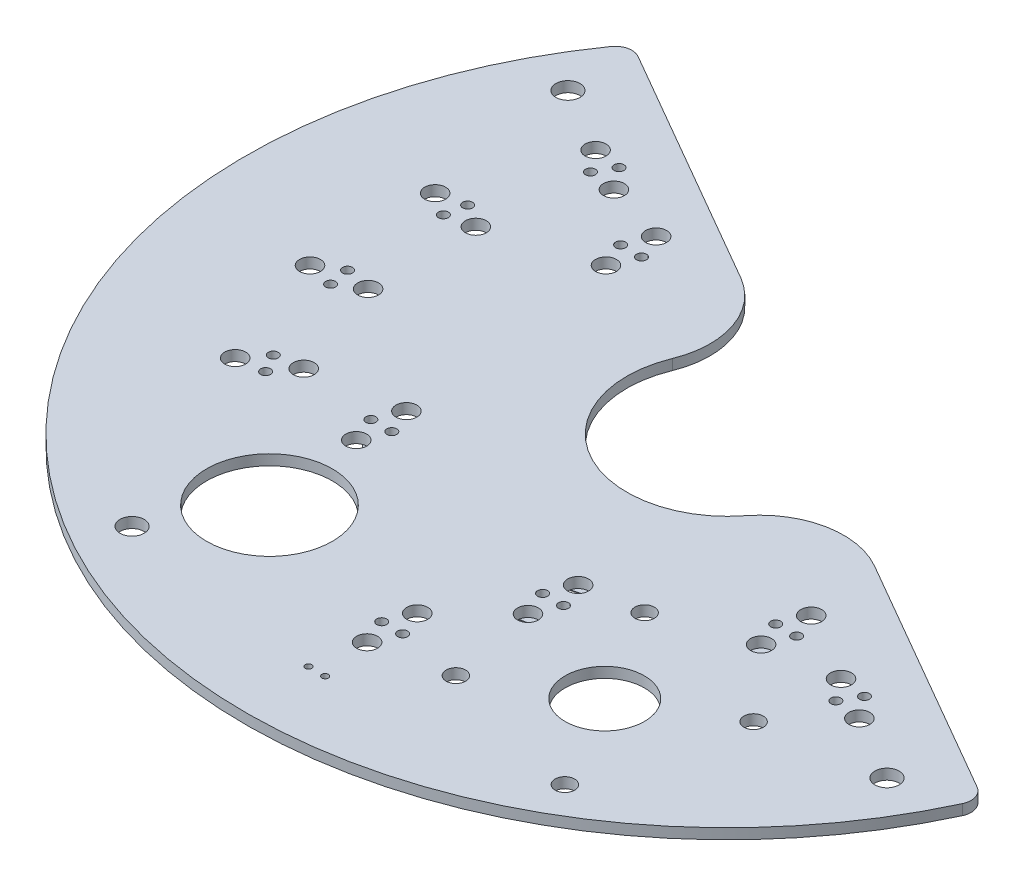
SolidWorks part; units mm, degrees
ref_plane "Front Plane" through (0, 0, 0) normal (0, 0, 1) x (1, 0, 0)
ref_plane "Top Plane" through (0, 0, 0) normal (0, 1, 0) x (1, 0, 0)
ref_plane "Right Plane" through (0, 0, 0) normal (1, 0, 0) x (0, 0, -1)
sketch "Sketch1" plane through (0, 0, 0) normal (0, 1, 0) x (1, 0, 0)
  line L0 (0, 50.8) -> (0, 59.6199) construction
  line L1 (0, 50.8) -> (11.3081, 50.8) construction
  line L2 (0, 0) -> (0, 47) construction
  line L3 (0, 0) -> (-46.286, 8.1615) construction
  line L4 (0, 0) -> (0, 47) construction
  line L5 (0, 0) -> (-46.286, -8.1615) construction
  line L6 (30.1421, -21.2511) -> (30.1421, -12.4312) construction
  line L7 (8.4732, -34.8981) -> (8.4732, -26.0782) construction
  line L8 (-27.3518, -25.0898) -> (-27.3518, -16.2699) construction
  line L9 (-31.3513, 16.7436) -> (-31.3513, 25.5635) construction
  circle A0 centre (0, 0) radius 50.8 construction
  circle A1 centre (0, 0) radius 15.24
  circle A2 centre (0, 0) radius 73.025
  circle A3 centre (0, 50.8) radius 6.3 construction
  circle A4 centre (25.4, 43.9941) radius 6.3 construction
  circle A5 centre (43.9941, 25.4) radius 6.3 construction
  circle A6 centre (50.8, 0) radius 6.3 construction
  circle A7 centre (43.9941, -25.4) radius 6.3 construction
  circle A8 centre (25.4, -43.9941) radius 6.3 construction
  circle A9 centre (0, -50.8) radius 6.3 construction
  circle A10 centre (-25.4, -43.9941) radius 6.3 construction
  circle A11 centre (-43.9941, -25.4) radius 6.3 construction
  circle A12 centre (-50.8, 0) radius 6.3 construction
  circle A13 centre (-43.9941, 25.4) radius 6.3 construction
  circle A14 centre (-25.4, 43.9941) radius 6.3 construction
  circle A15 centre (0, 50.8) radius 1.585 construction
  circle A16 centre (-1.585, 50.8) radius 0.75
  circle A17 centre (1.585, 50.8) radius 0.75
  circle A18 centre (0, 50.8) radius 3.8 construction
  circle A19 centre (0, 54.6) radius 1.585
  circle A20 centre (0, 47) radius 1.585
  circle A21 centre (47.285, 27.3) radius 1.585
  circle A22 centre (43.2016, 26.7727) radius 0.75
  circle A23 centre (44.7866, 24.0273) radius 0.75
  circle A24 centre (40.7032, 23.5) radius 1.585
  circle A25 centre (47.285, -27.3) radius 1.585
  circle A26 centre (44.7866, -24.0273) radius 0.75
  circle A27 centre (43.2016, -26.7727) radius 0.75
  circle A28 centre (40.7032, -23.5) radius 1.585
  circle A29 centre (0, -54.6) radius 1.585
  circle A30 centre (1.585, -50.8) radius 0.75
  circle A31 centre (-1.585, -50.8) radius 0.75
  circle A32 centre (0, -47) radius 1.585
  circle A33 centre (-47.285, -27.3) radius 1.585
  circle A34 centre (-43.2016, -26.7727) radius 0.75
  circle A35 centre (-44.7866, -24.0273) radius 0.75
  circle A36 centre (-40.7032, -23.5) radius 1.585
  circle A37 centre (-47.285, 27.3) radius 1.585
  circle A38 centre (-44.7866, 24.0273) radius 0.75
  circle A39 centre (-43.2016, 26.7727) radius 0.75
  circle A40 centre (-40.7032, 23.5) radius 1.585
  circle A41 centre (25.4, 43.9941) radius 20
  circle A42 centre (-25.4, -43.9941) radius 9.525
  circle A43 centre (25.4, -43.9941) radius 6
  circle A44 centre (-46.286, 8.1615) radius 1.585
  circle A45 centre (-50.3035, 7.2604) radius 0.75
  circle A46 centre (-49.753, 10.3822) radius 0.75
  circle A47 centre (-53.7705, 9.4812) radius 1.585
  circle A48 centre (-46.286, -8.1615) radius 1.585
  circle A49 centre (-49.753, -10.3822) radius 0.75
  circle A50 centre (-50.3035, -7.2604) radius 0.75
  circle A51 centre (-53.7705, -9.4812) radius 1.585
  circle A52 centre (30.1421, -21.2511) radius 6.3 construction
  circle A53 centre (30.1421, -21.2511) radius 1.585 construction
  circle A54 centre (28.5571, -21.2511) radius 0.75
  circle A55 centre (31.7271, -21.2511) radius 0.75
  circle A56 centre (30.1421, -21.2511) radius 3.8 construction
  circle A57 centre (30.1421, -17.4511) radius 1.585
  circle A58 centre (30.1421, -25.0511) radius 1.585
  circle A59 centre (8.4732, -34.8981) radius 6.3 construction
  circle A60 centre (8.4732, -34.8981) radius 1.585 construction
  circle A61 centre (6.8882, -34.8981) radius 0.75
  circle A62 centre (10.0582, -34.8981) radius 0.75
  circle A63 centre (8.4732, -34.8981) radius 3.8 construction
  circle A64 centre (8.4732, -31.0981) radius 1.585
  circle A65 centre (8.4732, -38.6981) radius 1.585
  circle A66 centre (-27.3518, -25.0898) radius 6.3 construction
  circle A67 centre (-27.3518, -25.0898) radius 1.585 construction
  circle A68 centre (-28.9368, -25.0898) radius 0.75
  circle A69 centre (-25.7668, -25.0898) radius 0.75
  circle A70 centre (-27.3518, -25.0898) radius 3.8 construction
  circle A71 centre (-27.3518, -21.2898) radius 1.585
  circle A72 centre (-27.3518, -28.8898) radius 1.585
  circle A73 centre (-31.3513, 16.7436) radius 6.3 construction
  circle A74 centre (-31.3513, 16.7436) radius 1.585 construction
  circle A75 centre (-32.9363, 16.7436) radius 0.75
  circle A76 centre (-29.7663, 16.7436) radius 0.75
  circle A77 centre (-31.3513, 16.7436) radius 3.8 construction
  circle A78 centre (-31.3513, 20.5436) radius 1.585
  circle A79 centre (-31.3513, 12.9436) radius 1.585
  point P50 (0, 0)
  point P84 (0, 0)
  dimension "D1" = 12
  dimension "D2" = 101.6
  dimension "D3" = 3.17
  dimension "D4" = 1.5
  dimension "D5" = 7.6
  dimension "D6" = 6
  dimension "D7" = 3.17
  dimension "D8" = 40
  dimension "D9" = 19.05
  dimension "D10" = 12
  dimension "D11" = 146.05
  dimension "D12" = 30.48
  dimension "D14" = 80
  dimension "D16" = 100
  dimension "D13" = 2
  dimension "D15" = 2
extrude "Boss-Extrude1" add sketch "Sketch1" against normal blind 1.5875
sketch "Sketch2" plane through (0, 0, 0) normal (0, 1, 0) x (1, 0, 0)
  line L0 (0, 0) -> (0, 66.04) construction
  line L1 (0, 0) -> (-57.1923, 33.02) construction
  circle A0 centre (0, 0) radius 66.04 construction
  circle A1 centre (0, 66.04) radius 1.8288 construction
  circle A2 centre (-57.1923, 33.02) radius 1.8288
  circle A3 centre (33.02, 57.1923) radius 1.8288
  circle A4 centre (57.1923, -33.02) radius 1.8288
  circle A5 centre (-33.02, -57.1923) radius 1.8288
  point P17 (0, 0)
  dimension "D1" = 132.08
  dimension "D2" = 3.6576
  dimension "D3" = 2
  dimension "D4" = 60
  dimension "D5" = 4
extrude "Cut-Extrude1" cut sketch "Sketch2" against normal through all
sketch "Sketch3" plane through (0, 0, 0) normal (0, 1, 0) x (1, 0, 0)
  line L0 (-57.1923, 33.02) -> (57.1923, -33.02) construction
  line L1 (-59.5338, 44.6372) -> (68.4238, -29.2392)
  line L2 (-52.7473, 40.719) -> (61.6373, -25.321) construction
  arc A0 (68.4238, -29.2392) -> (-59.5338, 44.6372) centre (0, 0) ccw
  dimension "D1" = 8.89
extrude "Cut-Extrude2" cut sketch "Sketch3" against normal through all
fillet "Fillet1" radius 12.7 2 edges at (15.165, -0.7937, -1.5098) (-6.275, -0.7937, -13.8882)
fillet "Fillet2" radius 2.54 2 edges at (67.2161, -0.7937, 28.542) (-58.3261, -0.7937, -43.9399)
sketch "Sketch4" plane through (0, 0, 0) normal (0, 1, 0) x (1, 0, 0)
  line L0 (0, 0) -> (0, -73.025) construction
  arc A0 (-59.6949, 42.0615) -> (66.2738, -30.6666) centre (0, 0) ccw construction
  circle A1 centre (0, 0) radius 62.23 construction
  circle A2 centre (0, -62.23) radius 0.4953 construction
  circle A3 centre (1.27, -62.23) radius 0.4953
  circle A4 centre (-1.27, -62.23) radius 0.4953
  dimension "D1" = 0.9906
  dimension "D4" = 124.46
  dimension "D2" = 2
  dimension "D3" = 2
extrude "Cut-Extrude3" cut sketch "Sketch4" against normal through all
sketch "Sketch5" plane through (0, -1.5875, 0) normal (0, -1, 0) x (1, 0, 0)
  line L13 (30.4135, 24.5983) -> (41.5359, 31.0198)
  line L14 (28.0125, 9.134) -> (57.7422, 26.2984)
  line L29 (46.7892, 22.3211) -> (54.7743, 26.9312)
  line L30 (29.0803, 12.0968) -> (45.0238, 21.3018)
  line L31 (6.096, 38.6381) -> (6.096, 51.4811)
  line L32 (29.8903, 21.9498) -> (40.9598, 28.3409)
  line L33 (-6.096, 38.6381) -> (-6.096, 51.4811)
  line L34 (4.064, 36.8606) -> (4.064, 49.6426)
  line L35 (-21.9165, -19.6925) -> (-41.5359, -31.0198)
  line L39 (-4.064, 36.8606) -> (-4.064, 49.6426)
  line L40 (-30.4135, 24.5983) -> (-41.5359, 31.0198)
  line L42 (-29.8903, 21.9498) -> (-40.9598, 28.3409)
  line L93 (-25.0163, -19.1359) -> (-40.9598, -28.3409)
  arc A0 (1.2946, 63.4357) -> (1.2454, 61.0243) centre (1.27, 62.23) ccw
  arc A1 (-1.1373, 61.0264) -> (-1.1844, 63.4379) centre (-1.27, 62.23) ccw
  arc A2 (-1.1373, 61.0264) -> (-54.0489, -28.3589) centre (0, 0) ccw
  arc A3 (-1.1844, 63.4379) -> (-56.1144, -29.6131) centre (0, 0) ccw
  arc A4 (54.7743, 26.9312) -> (1.2454, 61.0243) centre (0, 0) ccw
  arc A5 (-56.1144, -29.6131) -> (-54.0489, -28.3589) centre (-55.1689, -28.8424) ccw
  arc A6 (6.096, 51.4811) -> (2.3857, 51.7858) centre (0, 0) ccw
  arc A7 (29.8903, 21.9498) -> (4.064, 36.8606) centre (0, 0) ccw
  arc A8 (2.3857, 51.7858) -> (2.3071, 49.7553) centre (1.585, 50.8) ccw
  arc A9 (-2.3071, 49.7553) -> (-2.3857, 51.7858) centre (-1.585, 50.8) ccw
  arc A10 (-48.5987, -10.912) -> (-50.5848, -11.342) centre (-49.753, -10.3822) ccw
  arc A11 (-51.4133, -6.6431) -> (-49.4, -6.3679) centre (-50.3035, -7.2604) ccw
  arc A12 (46.0407, 23.8268) -> (44.2429, 22.8796) centre (44.7866, 24.0273) ccw
  arc A13 (41.9358, 26.8756) -> (43.655, 27.959) centre (43.2016, 26.7727) ccw
  arc A14 (-49.4, 6.3679) -> (-51.4133, 6.6431) centre (-50.3035, 7.2604) ccw
  arc A15 (-50.5848, 11.342) -> (-48.5987, 10.912) centre (-49.753, 10.3822) ccw
  arc A16 (57.7422, 26.2984) -> (1.2946, 63.4357) centre (0, 0) ccw
  arc A17 (-2.3857, 51.7858) -> (-6.096, 51.4811) centre (0, 0) ccw
  arc A18 (-2.3071, 49.7553) -> (-4.064, 49.6426) centre (0, 0) ccw
  arc A19 (45.0238, 21.3018) -> (44.2429, 22.8796) centre (0, 0) ccw
  arc A20 (29.0803, 12.0968) -> (-25.0163, -19.1359) centre (0, 0) ccw
  arc A21 (28.0125, 9.134) -> (-21.9165, -19.6925) centre (0, 0) ccw
  arc A22 (46.7892, 22.3211) -> (46.0407, 23.8268) centre (0, 0) ccw
  arc A23 (43.655, 27.959) -> (41.5359, 31.0198) centre (0, 0) ccw
  arc A24 (-46.0407, -23.8268) -> (-44.2429, -22.8796) centre (-44.7866, -24.0273) ccw
  arc A25 (-41.9358, -26.8756) -> (-43.655, -27.959) centre (-43.2016, -26.7727) ccw
  arc A26 (41.9358, 26.8756) -> (40.9598, 28.3409) centre (0, 0) ccw
  circle A27 centre (1.27, 62.23) radius 0.4953
  arc A28 (-43.655, 27.959) -> (-41.9358, 26.8756) centre (-43.2016, 26.7727) ccw
  arc A29 (-44.2429, 22.8796) -> (-46.0407, 23.8268) centre (-44.7866, 24.0273) ccw
  circle A30 centre (-1.27, 62.23) radius 0.4953
  arc A31 (-43.655, -27.959) -> (-41.5359, -31.0198) centre (0, 0) ccw
  circle A32 centre (-26.7727, 43.2016) radius 1.27 [skipped]
  circle A33 centre (-24.0273, 44.7866) radius 1.27 [skipped]
  circle A34 centre (24.0273, 44.7866) radius 1.27 [skipped]
  circle A35 centre (26.7727, 43.2016) radius 1.27 [skipped]
  circle A36 centre (50.8, 1.585) radius 1.27 [skipped]
  circle A37 centre (50.8, -1.585) radius 1.27 [skipped]
  circle A38 centre (44.7866, -24.0273) radius 1.27 [skipped]
  circle A39 centre (43.2016, -26.7727) radius 1.27 [skipped]
  circle A40 centre (26.7727, -43.2016) radius 1.27 [skipped]
  circle A41 centre (24.0273, -44.7866) radius 1.27 [skipped]
  circle A42 centre (1.585, -50.8) radius 1.27 [skipped]
  circle A43 centre (-1.585, -50.8) radius 1.27 [skipped]
  circle A44 centre (-24.0273, -44.7866) radius 1.27 [skipped]
  circle A45 centre (-26.7727, -43.2016) radius 1.27 [skipped]
  circle A46 centre (-50.8, 1.585) radius 1.27 [skipped]
  circle A47 centre (-50.8, -1.585) radius 1.27 [skipped]
  arc A48 (-41.9358, -26.8756) -> (-40.9598, -28.3409) centre (0, 0) ccw
  arc A49 (-40.9598, 28.3409) -> (-41.9358, 26.8756) centre (0, 0) ccw
  arc A50 (30.4135, 24.5983) -> (6.096, 38.6381) centre (0, 0) ccw
  circle A51 centre (1.585, 50.8) radius 0.75
  arc A52 (-46.0407, 23.8268) -> (-47.6319, 20.4612) centre (0, 0) ccw
  arc A53 (4.064, 49.6426) -> (2.3071, 49.7553) centre (0, 0) ccw
  arc A54 (-41.5359, 31.0198) -> (-43.655, 27.959) centre (0, 0) ccw
  arc A55 (-6.096, 38.6381) -> (-30.4135, 24.5983) centre (0, 0) ccw
  arc A56 (-4.064, 36.8606) -> (-29.8903, 21.9498) centre (0, 0) ccw
  arc A57 (-44.2429, 22.8796) -> (-48.5987, 10.912) centre (0, 0) ccw
  circle A58 centre (-1.585, 50.8) radius 0.75
  circle A59 centre (43.2016, 26.7727) radius 0.75
  arc A60 (-47.6319, 20.4612) -> (-50.5848, 11.342) centre (0, 0) ccw
  arc A61 (-51.4133, 6.6431) -> (-51.4133, -6.6431) centre (0, 0) ccw
  arc A62 (-49.4, 6.3679) -> (-49.4, -6.3679) centre (0, 0) ccw
  circle A63 centre (44.7866, 24.0273) radius 0.75
  arc A64 (-50.5848, -11.342) -> (-46.0407, -23.8268) centre (0, 0) ccw
  arc A65 (-48.5987, -10.912) -> (-44.2429, -22.8796) centre (0, 0) ccw
  circle A66 centre (-43.2016, 26.7727) radius 0.75
  circle A67 centre (-44.7866, 24.0273) radius 0.75
  circle A68 centre (-49.753, 10.3822) radius 0.75
  circle A69 centre (-50.3035, 7.2604) radius 0.75
  circle A70 centre (-50.3035, -7.2604) radius 0.75
  circle A71 centre (-49.753, -10.3822) radius 0.75
  circle A72 centre (-44.7866, -24.0273) radius 0.75
  circle A73 centre (-43.2016, -26.7727) radius 0.75
  point P35 (0, 0)
  point P41 (0, 0)
  point P42 (-54.2332, -28.0055)
  point P45 (-55.1689, -28.8424)
  point P50 (0, 0)
  point P51 (0, 0)
  point P52 (0, 0)
  point P53 (0, 0)
  point P54 (0, 0)
  dimension "D13" = 12
  dimension "D15" = 3
extrude "Boss-Extrude2" add sketch "Sketch5" along normal blind 0.1016
sketch "Sketch6" plane through (0, -1.5875, 0) normal (0, -1, 0) x (1, 0, 0)
  line L0 (0, 0) -> (25.4, 43.9941) construction
  line L1 (25.4, 43.9941) -> (36.5125, 63.2415) construction
  circle A0 centre (25.4, 43.9941) radius 16.51 construction
  arc A1 (66.2738, 30.6666) -> (-59.6949, -42.0615) centre (0, 0) ccw construction
  circle A2 centre (33.655, 58.2922) radius 1.4732
  circle A3 centre (11.1019, 52.2491) radius 1.4732
  circle A4 centre (17.145, 29.696) radius 1.4732
  circle A5 centre (39.6981, 35.7391) radius 1.4732
  point P20 (25.4, 43.9941)
  dimension "D1" = 2.9464
extrude "Cut-Extrude4" cut sketch "Sketch6" against normal through all
